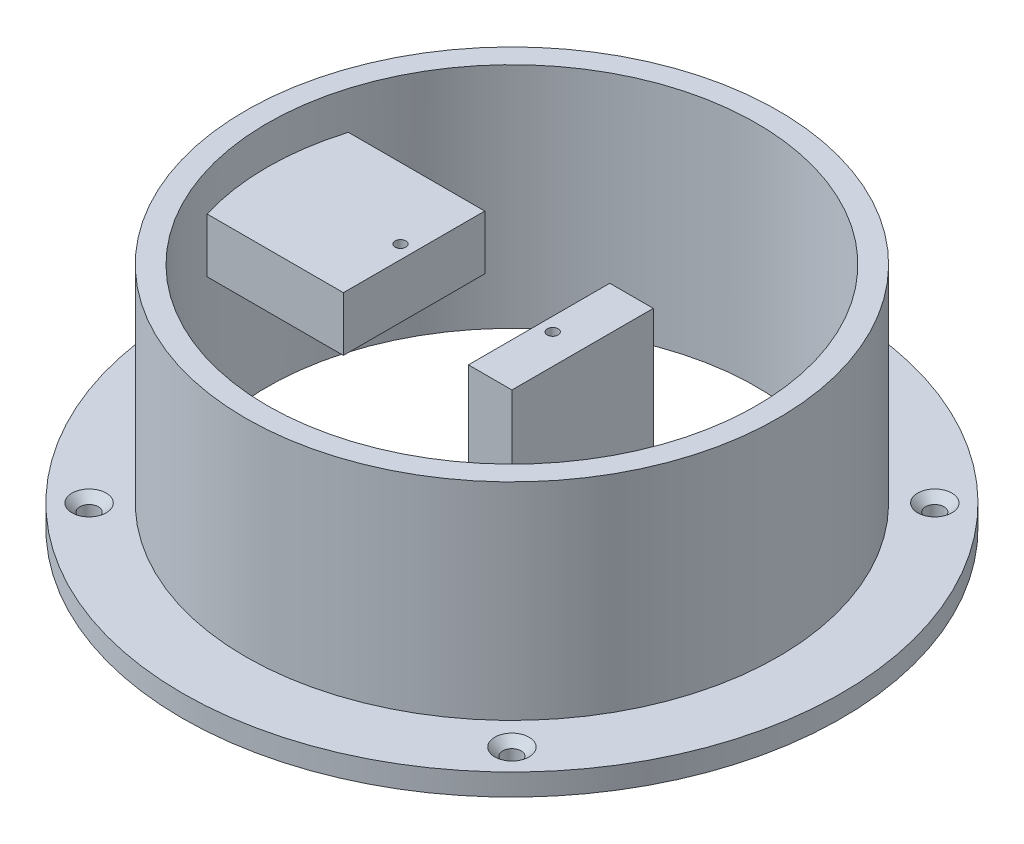
SolidWorks part; units mm, degrees
ref_plane "Front Plane" through (0, 0, 0) normal (0, 0, 1) x (1, 0, 0)
ref_plane "Top Plane" through (0, 0, 0) normal (0, 1, 0) x (1, 0, 0)
ref_plane "Right Plane" through (0, 0, 0) normal (1, 0, 0) x (0, 0, -1)
sketch "Sketch1" plane through (0, 0, 0) normal (0, 1, 0) x (1, 0, 0)
  circle A0 centre (0, 0) radius 60.625
  circle A1 centre (0, 0) radius 45
  dimension "D1" = 121.25
  dimension "D2" = 90
extrude "Boss-Extrude1" add sketch "Sketch1" along normal blind 4
sketch "Sketch2" plane through (0, 4, 0) normal (0, 1, 0) x (1, 0, 0)
  circle A0 centre (0, 0) radius 45 construction
  circle A1 centre (0, 0) radius 45
  circle A2 centre (0, 0) radius 49
  dimension "D1" = 4
extrude "Boss-Extrude2" add sketch "Sketch2" along normal blind 38
ref_plane "Plane1" through (0, 22, 0) normal (0, 1, 0) x (1, 0, 0)
sketch "Sketch4" plane through (0, 0, 0) normal (0, 0, 1) x (1, 0, 0)
  line L0 (-60.625, 0) -> (60.625, 0) construction
  line L1 (5, 35) -> (13, 35)
  line L2 (5, 35) -> (5, 0)
  line L3 (5, 0) -> (13, 0)
  line L4 (13, 35) -> (13, 0)
  line L5 (49, 42) -> (-49, 42) construction
  line L6 (-45, 42) -> (-45, 4)
  line L7 (-18, 35) -> (-45, 35)
  line L8 (-18, 35) -> (-18, 25)
  line L9 (-18, 25) -> (-45, 25)
  line L10 (-45, 35) -> (-45, 25)
  line L11 (60.625, 4) -> (-60.625, 4) construction
  line L12 (-18, 25) -> (-45, -2)
  dimension "D1" = 5
  dimension "D2" = 8
  dimension "D3" = 7
  dimension "D4" = 23
  dimension "D5" = 27
  dimension "D6" = 10
  dimension "D7" = 45
  dimension "D8" = 7
extrude "Boss-Extrude4" add sketch "Sketch4" along normal mid plane 26 contours L9 L8 L7 L6 | L12 L9 L6 | L1 L4 L3 L2 region at (-31.5, 30, 0)
sketch "Sketch5" plane through (0, 0, 0) normal (0, -1, 0) x (1, 0, 0)
  line L0 (3.3931, 14.5721) -> (34.8417, 28.479)
  line L1 (3.3931, -12.7877) -> (35.3292, -27.872)
  line L2 (3.3931, 14.5721) -> (3.3931, -12.7877)
  circle A0 centre (0, 0) radius 45 construction
  arc A1 (35.3292, -27.872) -> (34.8417, 28.479) centre (0, 0) ccw
extrude "Boss-Extrude5" add sketch "Sketch5" against normal up to surface (4 mm away) contours L0 A1 L1 L2 up to face at (0, 4, 60.625)
sketch "Sketch7" plane through (0, 35, 0) normal (0, 1, 0) x (1, 0, 0)
  line L0 (-18, -13) -> (-18, 13) construction
  circle A0 centre (-20.5, 5) radius 1.3
  circle A1 centre (-20.5, -5) radius 1.3
  circle A2 centre (27.5, 5) radius 1.3
  circle A3 centre (27.5, -5) radius 1.3
  dimension "D1" = 2.6
  dimension "D2" = 2.6
  dimension "D3" = 10
  dimension "D4" = 5
  dimension "D5" = 2.5
  dimension "D7" = 48
  dimension "D6" = 2
sketch "Sketch12" plane through (0, 4, 0) normal (0, 1, 0) x (1, 0, 0)
  line L3 (11.3931, 7.7188) -> (11.3931, -9.3624)
  line L4 (11.3931, 7.7188) -> (11.3931, -9.3624)
  line L9 (18, 10.8394) -> (18, -12.2841)
  line L10 (13, -13) -> (13, 13) construction
  line L18 (11.3931, -9.3624) -> (32.0457, -18.4953)
  line L19 (32.4985, 17.6875) -> (11.3931, 7.7188)
  line L21 (18, -12.2841) -> (32.0457, -18.4953)
  line L22 (32.4985, 17.6875) -> (18, 10.8394)
  arc A2 (32.0457, -18.4953) -> (32.4985, 17.6875) centre (0, 0) ccw
  arc A3 (32.0457, -18.4953) -> (32.4985, 17.6875) centre (0, 0) ccw
  dimension "D2" = 5
  dimension "D1" = 8
extrude "Cut-Extrude9" cut sketch "Sketch12" against normal through all contours L21 A3 L22 | L22 L9 L21 region at (27.4858, 4, 0.4769)
sketch "Sketch14" plane through (0, 4, 0) normal (0, 1, 0) x (1, 0, 0)
  line L0 (0, 0) -> (-38.8909, 38.8909) construction
  line L1 (5, 13) -> (13, 13) construction
  circle A0 centre (-38.8909, 38.8909) radius 1.5
  circle A1 centre (38.8909, 38.8909) radius 1.5
  circle A2 centre (38.8909, -38.8909) radius 1.5
  circle A3 centre (-38.8909, -38.8909) radius 1.5
  point P15 (0, 0)
  dimension "D1" = 3
  dimension "D2" = 55
  dimension "D3" = 135
  dimension "D4" = 4
hole_wizard "CSK for M3 Countersunk Flat Head Screw1" positions "Sketch15" profile "Sketch17" countersink size "M3" standard "DIN" end condition up to next
sketch "Sketch15" plane through (0, 4, 0) normal (0, 1, 0) x (1, 0, 0)
  point P0 (-38.8909, 38.8909)
  point P3 (-38.8909, -38.8909)
  point P6 (38.8909, -38.8909)
  point P9 (38.8909, 38.8909)
sketch "Sketch17" plane through (-38.8909, 4, -38.8909) normal (1, 0, 0) x (0, 0, 1)
  line L0 (0, 0) -> (0, 4)
  line L1 (0, 4) -> (1.7, 4)
  line L2 (1.7, 4) -> (1.7, 1.45)
  line L3 (1.7, 1.45) -> (3.15, 0)
  line L5 (3.15, 0) -> (0, 0)
  line L6 (-1.7, 1.45) -> (-3.15, 0) construction
  line L11 (0, -6.35) -> (0, 107.95) construction
  dimension "Thru Hole Dia." = 3.4
  dimension "Thru Hole Depth" = 4
  dimension "Near C'Sink Dia." = 6.3
  dimension "Near C'Sink Angle" = 90
sketch "Sketch18" plane through (0, 35, 0) normal (0, 1, 0) x (1, 0, 0)
  line L0 (-18, -13) -> (-18, 13) construction
  line L1 (5, -13) -> (5, 13) construction
  circle A0 centre (-20.5, 0) radius 1
  circle A1 centre (7.5, 0) radius 1
  point P4 (-18, 0)
  dimension "D1" = 2.5
  dimension "D2" = 2.5
extrude "Cut-Extrude10" cut sketch "Sketch18" against normal blind 4.5 contours A0
extrude "Cut-Extrude11" cut sketch "Sketch18<3>" against normal blind 4.5
sketch "Sketch18<3>" plane through (0, 35, 0) normal (0, 1, 0) x (1, 0, 0) same geometry as "Sketch18"
